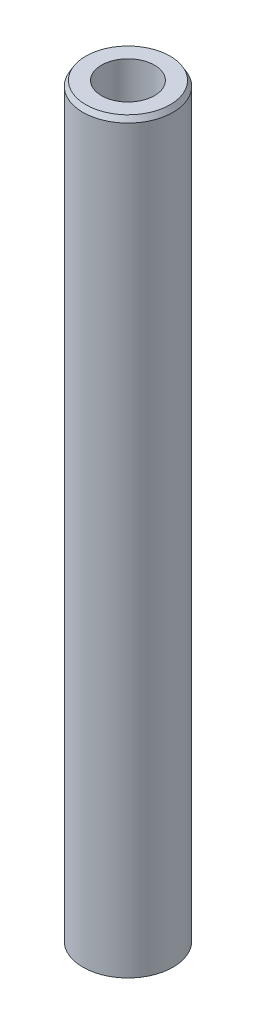
SolidWorks part; units mm, degrees
ref_plane "Front Plane" through (0, 0, 0) normal (0, 0, 1) x (1, 0, 0)
ref_plane "Top Plane" through (0, 0, 0) normal (0, 1, 0) x (1, 0, 0)
ref_plane "Right Plane" through (0, 0, 0) normal (1, 0, 0) x (0, 0, -1)
sketch "Sketch1" plane through (0, 0, 0) normal (0, 1, 0) x (1, 0, 0)
  circle A0 centre (0, 0) radius 35
  dimension "SHAFT_OD" = 70
extrude "Boss-Extrude1" add sketch "Sketch1" along normal blind 580.8909
sketch "Sketch2" plane through (0, 0, 0) normal (0, 1, 0) x (1, 0, 0)
  circle A0 centre (0, 0) radius 20.555
  dimension "BORE_D" = 41.11
extrude "Cut-Extrude1" cut sketch "Sketch2" along normal through all
chamfer "Chamfer1" distance 3.9648 angle 30 2 edges at (0, 580.8909, 35) (0, 0, 35) first distance on face at (0, 580.8909, 35) first distance on face at (0, 0, 20.555)
